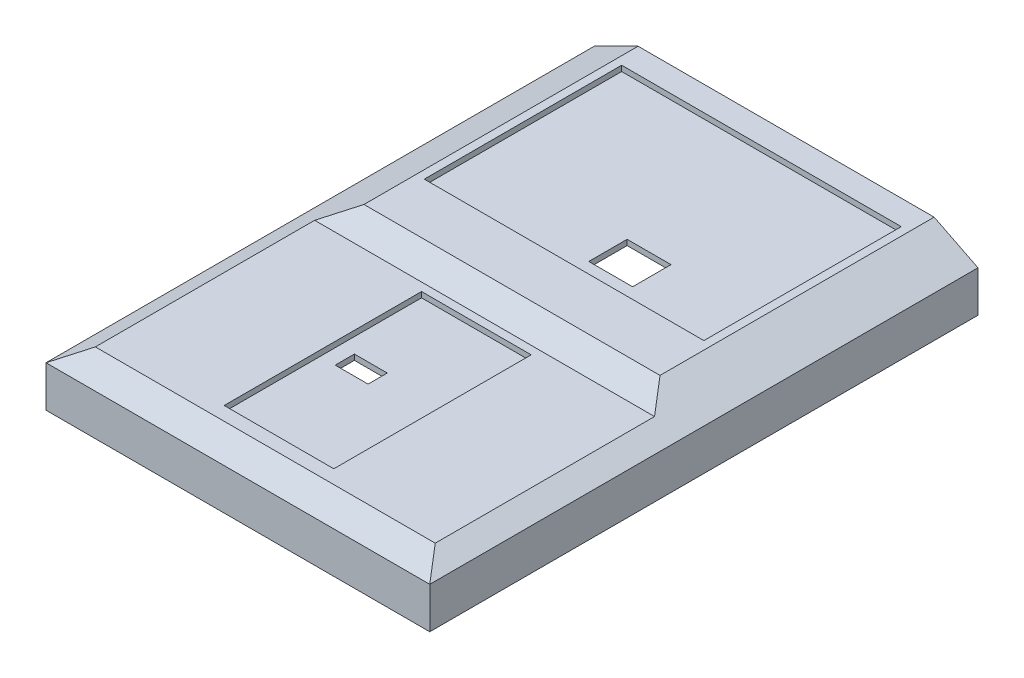
SolidWorks part; units mm, degrees
ref_plane "Ebene vorne" through (0, 0, 0) normal (0, 0, 1) x (1, 0, 0)
ref_plane "Ebene oben" through (0, 0, 0) normal (0, 1, 0) x (1, 0, 0)
ref_plane "Ebene rechts" through (0, 0, 0) normal (1, 0, 0) x (0, 0, -1)
sketch "Skizze1" plane through (0, 0, 0) normal (0, 0, 1) x (1, 0, 0)
  line L1 (-35, -7.5) -> (35, -7.5)
  line L2 (-35, -7.5) -> (-35, 7.5)
  line L3 (-35, 7.5) -> (35, 7.5)
  line L4 (35, -7.5) -> (35, 7.5)
  line L5 (-35, -7.5) -> (35, 7.5) construction
  line L6 (-35, 7.5) -> (35, -7.5) construction
  point P0 (0, 0)
  dimension "D1" = 70
  dimension "D2" = 15
extrude "Aufsatz-Linear austragen1" add sketch "Skizze1" along normal blind 100
sketch "Skizze2" plane through (0, 0, 100) normal (0, 0, 1) x (1, 0, 0)
  line L0 (-35, 7.5) -> (-35, 0)
  line L1 (-35, 7.5) -> (-35, -7.5) construction
  line L2 (-35, 0) -> (-20, 7.5)
  line L3 (35, 7.5) -> (-35, 7.5) construction
  line L4 (-20, 7.5) -> (-35, 7.5)
  dimension "D1" = 15
extrude "Schnitt-Linear austragen1" cut sketch "Skizze2" against normal up to surface (100 mm away) up to face at (0, 0, 0)
ref_plane "Ebene1" through (0, 0, 0) normal (-1, 0, 0) x (0, 0, 1)
mirror "Spiegeln1" about plane through (0, 0, 0) normal (-1, 0, 0) of "Schnitt-Linear austragen1"
sketch "Skizze4" plane through (-35, 0, 0) normal (-1, 0, 0) x (0, 0, 1)
  line L0 (100, 0) -> (95, 2)
  line L1 (95, 2) -> (55, 2)
  line L2 (55, 2) -> (50, 4)
  line L3 (50, 4) -> (0, 4)
  line L5 (0, 7.5) -> (100, 7.5) construction
  line L6 (0, 7.5) -> (100, 7.5)
  line L7 (100, 7.5) -> (100, 0)
  line L8 (0, 0) -> (0, 7.5) construction
  line L9 (0, 4) -> (0, 7.5)
  dimension "D1" = 2
  dimension "D2" = 2
  dimension "D3" = 40
  dimension "D4" = 50
extrude "Schnitt-Linear austragen3" cut sketch "Skizze4" against normal up to surface (70 mm away) up to face at (35, -3.75, 50)
shell "Wandung1" thickness 2 removed face at (0, -7.5, 50)
sketch "Skizze5" plane through (0, 2, 0) normal (0, 1, 0) x (1, 0, 0)
  line L0 (0, 4.125) -> (0, -4.125) construction
  line L1 (-10, -92.5) -> (10, -92.5)
  line L2 (-10, -92.5) -> (-10, -56.5)
  line L3 (-10, -56.5) -> (10, -56.5)
  line L4 (10, -92.5) -> (10, -56.5)
  line L5 (-10, -92.5) -> (10, -56.5) construction
  line L6 (-10, -56.5) -> (10, -92.5) construction
  line L7 (31, -55) -> (-31, -55) construction
  point P0 (0, -74.5)
  dimension "D1" = 36
  dimension "D2" = 20
  dimension "D3" = 1.5
extrude "Schnitt-Linear austragen4" cut sketch "Skizze5" against normal blind 1
sketch "Skizze6" plane through (0, 1, 0) normal (0, 1, 0) x (1, 0, 0)
  line L0 (-10, -56.5) -> (-10, -92.5) construction
  line L1 (-7.25, -71.5) -> (-1.25, -71.5)
  line L2 (-7.25, -71.5) -> (-7.25, -75)
  line L3 (-7.25, -75) -> (-1.25, -75)
  line L4 (-1.25, -71.5) -> (-1.25, -75)
  line L5 (10, -56.5) -> (-10, -56.5) construction
  dimension "D1" = 2.75
  dimension "D2" = 15
  dimension "D3" = 3.5
  dimension "D4" = 6
extrude "Schnitt-Linear austragen5" cut sketch "Skizze6" against normal up to surface (1 mm away) up to face at (0, 0, 74.6148)
sketch "Skizze7" plane through (0, 4, 0) normal (0, 1, 0) x (1, 0, 0)
  line L1 (25.5, -4.5) -> (-25.5, -4.5)
  line L2 (25.5, -4.5) -> (25.5, -40.5)
  line L3 (25.5, -40.5) -> (-25.5, -40.5)
  line L4 (-25.5, -4.5) -> (-25.5, -40.5)
  line L5 (25.5, -4.5) -> (-25.5, -40.5) construction
  line L6 (25.5, -40.5) -> (-25.5, -4.5) construction
  line L7 (27, -50) -> (27, 0) construction
  line L8 (27, 0) -> (-27, 0) construction
  point P0 (0, -22.5)
  dimension "D1" = 51
  dimension "D2" = 36
  dimension "D3" = 1.5
  dimension "D4" = 4.5
extrude "Schnitt-Linear austragen6" cut sketch "Skizze7" against normal blind 1
sketch "Skizze12" plane through (0, 3, 0) normal (0, 1, 0) x (1, 0, 0)
  line L0 (25.5, -40.5) -> (25.5, -4.5) construction
  line L1 (9.5, -37.5) -> (1.5, -37.5)
  line L2 (9.5, -37.5) -> (9.5, -30.5)
  line L3 (9.5, -30.5) -> (1.5, -30.5)
  line L4 (1.5, -37.5) -> (1.5, -30.5)
  line L5 (25.5, -4.5) -> (-25.5, -4.5) construction
  dimension "D1" = 7
  dimension "D2" = 8
  dimension "D3" = 16
  dimension "D4" = 26
extrude "Schnitt-Linear austragen8" cut sketch "Skizze12" against normal up to surface (1 mm away) up to face at (0, 2, 25.8074)
sketch "Skizze13" plane through (0, 0, 0) normal (0, 0, -1) x (-1, 0, 0)
  line L0 (2.5, -7.5) -> (-2.5, -7.5)
  line L1 (35, -7.5) -> (-35, -7.5) construction
  line L2 (-2.5, -7.5) -> (-2.5, -6.2)
  line L3 (-2.5, -6.2) -> (-7.5, -6.2)
  line L4 (-7.5, -6.2) -> (-7.5, -4.5)
  line L5 (-7.5, -4.5) -> (7.5, -4.5)
  line L6 (7.5, -4.5) -> (7.5, -6.2)
  line L7 (7.5, -6.2) -> (2.5, -6.2)
  line L8 (2.5, -6.2) -> (2.5, -7.5)
  line L9 (0, -4.125) -> (0, 4.125) construction
  dimension "D1" = 2.5
  dimension "D2" = 2.5
  dimension "D3" = 5
  dimension "D4" = 5
  dimension "D5" = 1.3
  dimension "D6" = 1.7
extrude "Schnitt-Linear austragen9" cut sketch "Skizze13" against normal blind 1
